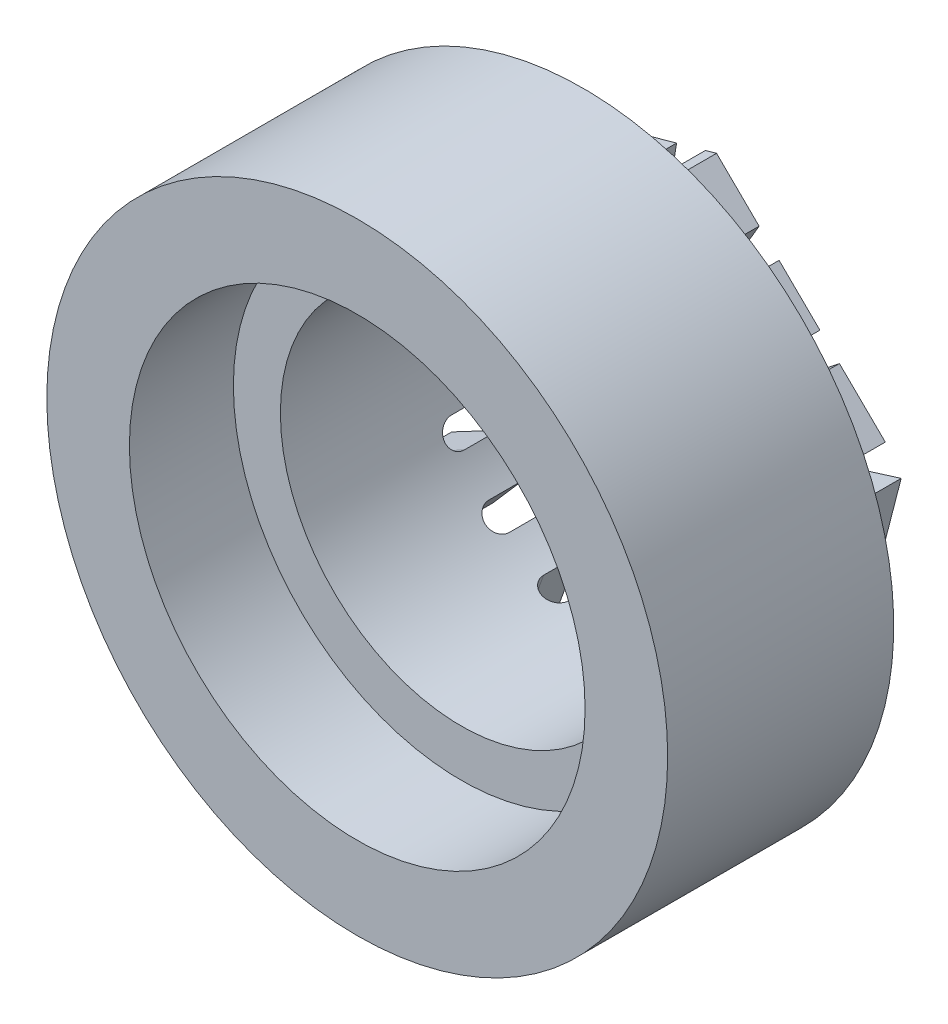
SolidWorks part; units mm, degrees
material "AISI Type 316L stainless steel"
ref_plane "Front Plane" through (0, 0, 0) normal (0, 0, 1) x (1, 0, 0)
ref_plane "Top Plane" through (0, 0, 0) normal (0, 1, 0) x (1, 0, 0)
ref_plane "Right Plane" through (0, 0, 0) normal (1, 0, 0) x (0, 0, -1)
sketch "Sketch1" plane through (0, 0, 0) normal (0, 0, 1) x (1, 0, 0)
  circle A0 centre (0, 0) radius 21.7995
  dimension "D1" = 43.5991
extrude "Boss-Extrude1" add sketch "Sketch1" along normal blind 20.6502
sketch "Sketch2" plane through (0, 0, 20.6502) normal (0, 0, 1) x (1, 0, 0)
  circle A0 centre (0, 0) radius 12.7
  dimension "D1" = 25.4
extrude "Cut-Extrude1" cut sketch "Sketch2" against normal blind 20.6502
sketch "Sketch3" plane through (0, 0, 20.6502) normal (0, 0, 1) x (1, 0, 0)
  circle A0 centre (0, 0) radius 16
  dimension "D1" = 32
extrude "Cut-Extrude2" cut sketch "Sketch3" against normal blind 7.3025
sketch "Sketch4" plane through (0, 0, 0) normal (0, 0, -1) x (-1, 0, 0)
  line L1 (17.6618, -4.9073) -> (13.0808, 12.8419)
  line L2 (13.0808, 12.8419) -> (-4.581, 17.7492)
  line L3 (-4.581, 17.7492) -> (-17.6618, 4.9073)
  line L4 (-17.6618, 4.9073) -> (-13.0808, -12.8419)
  line L5 (-13.0808, -12.8419) -> (4.581, -17.7492)
  line L6 (4.581, -17.7492) -> (17.6618, -4.9073)
  circle A1 centre (0, 0) radius 15.875 construction
  dimension "D1" = 31.75
extrude "Cut-Extrude3" cut sketch "Sketch4" against normal blind 4.7752 flip side to cut
sketch "Sketch5" plane through (-15.3713, 3.9673, 0) normal (-0.9683, 0.2499, 0) x (0, 0, 1)
  line L0 (0, 0) -> (4.7752, 0) construction
  line L1 (4.7752, -9.1654) -> (4.7752, 9.1654) construction
  line L2 (2.3876, 0.9525) -> (0, 0.9525)
  line L3 (0, -9.1654) -> (0, 9.1654) construction
  line L4 (0, 0.9525) -> (0, -0.9525)
  line L5 (0, -0.9525) -> (2.3876, -0.9525)
  arc A1 (2.3876, 0.9525) -> (2.3876, -0.9525) centre (2.3876, 0) cw
extrude "Cut-Extrude4" cut sketch "Sketch5" against normal blind 9.8552 and the other way blind 9.8552
pattern_circular "CirPattern1" count 17 over 360 about axis through (0, 0, 13.3477) along (0, 0, 1) of "Cut-Extrude4" reverse direction yes
